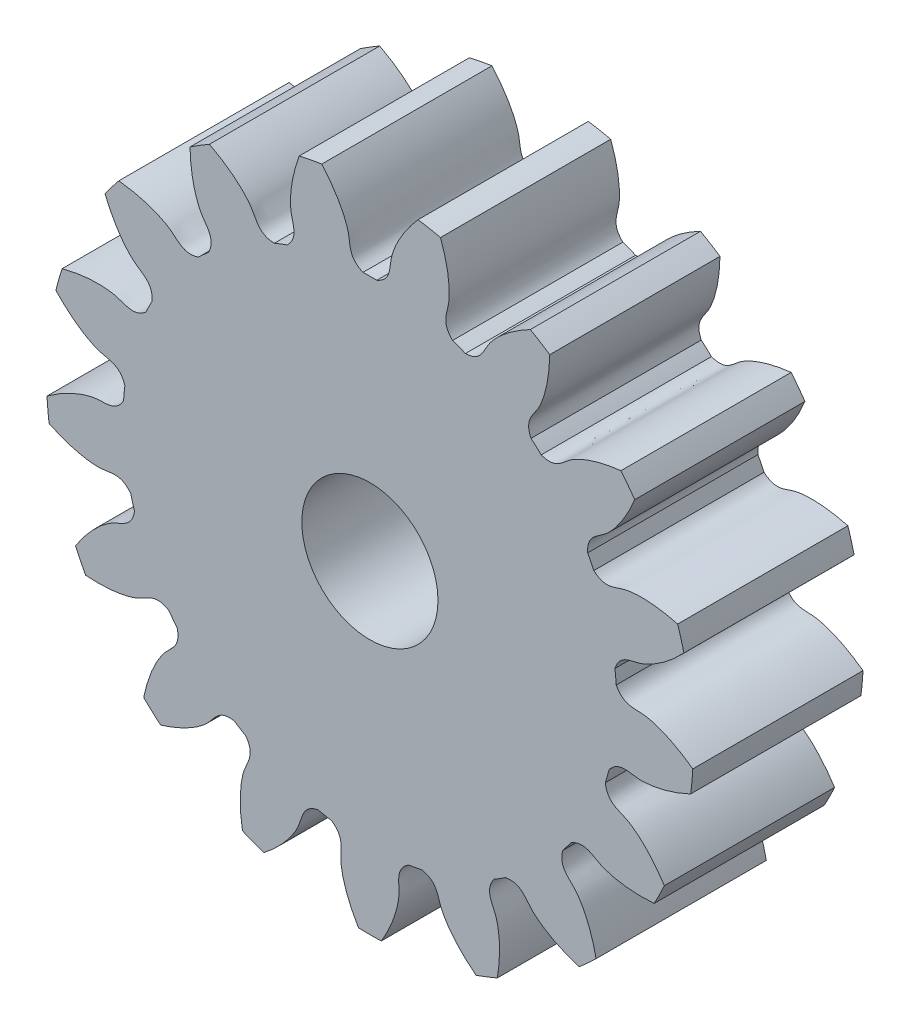
SolidWorks part; units mm, degrees
ref_plane "前视基准面" through (0, 0, 0) normal (0, 0, 1) x (1, 0, 0)
ref_plane "上视基准面" through (0, 0, 0) normal (0, 1, 0) x (1, 0, 0)
ref_plane "右视基准面" through (0, 0, 0) normal (1, 0, 0) x (0, 0, -1)
sketch "草图1" plane through (0, 0, 0) normal (0, 0, 1) x (1, 0, 0)
  circle A0 centre (0, 0) radius 19
extrude "凸台-拉伸1" add sketch "草图1" along normal blind 10
ref_axis "基准轴1" through (0, 0, -1.5) along (0, 0, 1)
sketch "草图2" plane through (0, 0, 0) normal (0, 0, 1) x (1, 0, 0)
  line L0 (0, 0) -> (0, 19) construction
  circle A0 centre (0, 0) radius 19 construction
  arc A1 (0.4034, 14.4944) -> (-0.4034, 14.4944) centre (0, 0) ccw
  arc A2 (6.2313, 21.4814) -> (-6.2313, 21.4814) centre (0, 0) ccw
  spline S0 degree 3 poles (0.4034, 14.4944) (1.2558, 14.8496) (1.1324, 15.5096) (1.2766, 16.1296) (1.29, 16.1823) (1.306, 16.2408) (1.3251, 16.3052) (1.3474, 16.3752) (1.3731, 16.4508) (1.4025, 16.5319) (1.4359, 16.6184) (1.4733, 16.7101) (1.5152, 16.8068) (1.5616, 16.9086) (1.6128, 17.0151) (1.669, 17.1264) (1.7304, 17.2421) (1.7972, 17.3621) (1.8696, 17.4863) (1.9478, 17.6145) (2.032, 17.7465) (2.1224, 17.8821) (2.2191, 18.0211) (2.3223, 18.1634) (2.4322, 18.3086) (2.5489, 18.4566) (2.6727, 18.6072) (2.8035, 18.7601) (2.9417, 18.9152) (3.0873, 19.0722) (3.2404, 19.2308) (3.4012, 19.3908) (3.5698, 19.552) (3.7462, 19.7141) (3.9307, 19.8769) (4.1233, 20.0401) (4.324, 20.2035) (4.533, 20.3667) (4.7503, 20.5295) (4.9761, 20.6917) (5.2103, 20.853) (5.453, 21.0131) (5.7916, 21.2269) (6.0532, 21.3811) (6.2313, 21.4814) knots 0 0 0 0 0.193883 0.199024 0.204851 0.211363 0.21856 0.226443 0.235011 0.244265 0.254205 0.264829 0.27614 0.288136 0.300817 0.314184 0.328236 0.342973 0.358397 0.374505 0.391299 0.408779 0.426944 0.445795 0.465331 0.485552 0.506459 0.528051 0.550329 0.573293 0.596941 0.621276 0.646296 0.672001 0.698392 0.725468 0.753229 0.781677 0.810809 0.840627 0.871131 0.90232 0.934195 1 1 1 1
  spline S1 degree 3 poles (-0.4034, 14.4944) (-1.2558, 14.8496) (-1.1324, 15.5096) (-1.2766, 16.1296) (-1.29, 16.1823) (-1.306, 16.2408) (-1.3251, 16.3052) (-1.3474, 16.3752) (-1.3731, 16.4508) (-1.4025, 16.5319) (-1.4359, 16.6184) (-1.4733, 16.7101) (-1.5152, 16.8068) (-1.5616, 16.9086) (-1.6128, 17.0151) (-1.669, 17.1264) (-1.7304, 17.2421) (-1.7972, 17.3621) (-1.8696, 17.4863) (-1.9478, 17.6145) (-2.032, 17.7465) (-2.1224, 17.8821) (-2.2191, 18.0211) (-2.3223, 18.1634) (-2.4322, 18.3086) (-2.5489, 18.4566) (-2.6727, 18.6072) (-2.8035, 18.7601) (-2.9417, 18.9152) (-3.0873, 19.0722) (-3.2404, 19.2308) (-3.4012, 19.3908) (-3.5698, 19.552) (-3.7462, 19.7141) (-3.9307, 19.8769) (-4.1233, 20.0401) (-4.324, 20.2035) (-4.533, 20.3667) (-4.7503, 20.5295) (-4.9761, 20.6917) (-5.2103, 20.853) (-5.453, 21.0131) (-5.7916, 21.2269) (-6.0532, 21.3811) (-6.2313, 21.4814) knots 0 0 0 0 0.193883 0.199024 0.204851 0.211363 0.21856 0.226443 0.235011 0.244265 0.254205 0.264829 0.27614 0.288136 0.300817 0.314184 0.328236 0.342973 0.358397 0.374505 0.391299 0.408779 0.426944 0.445795 0.465331 0.485552 0.506459 0.528051 0.550329 0.573293 0.596941 0.621276 0.646296 0.672001 0.698392 0.725468 0.753229 0.781677 0.810809 0.840627 0.871131 0.90232 0.934195 1 1 1 1
extrude "切除-拉伸1" cut sketch "草图2" along normal through all
pattern_circular "阵列(圆周)1" count 17 every 21.176 about axis through (0, 0, -1.5) along (0, 0, 1) of "切除-拉伸1"
sketch "草图3" plane through (0, 0, 0) normal (0, 0, 1) x (1, 0, 0)
  circle A0 centre (0, 0) radius 17 construction
  dimension "Dn" = 34
sketch "草图4" plane through (0, 0, 10) normal (0, 0, 1) x (1, 0, 0)
  circle A0 centre (0, 0) radius 4
  dimension "D1" = 8
extrude "切除-拉伸2" cut sketch "草图4" against normal up to next
